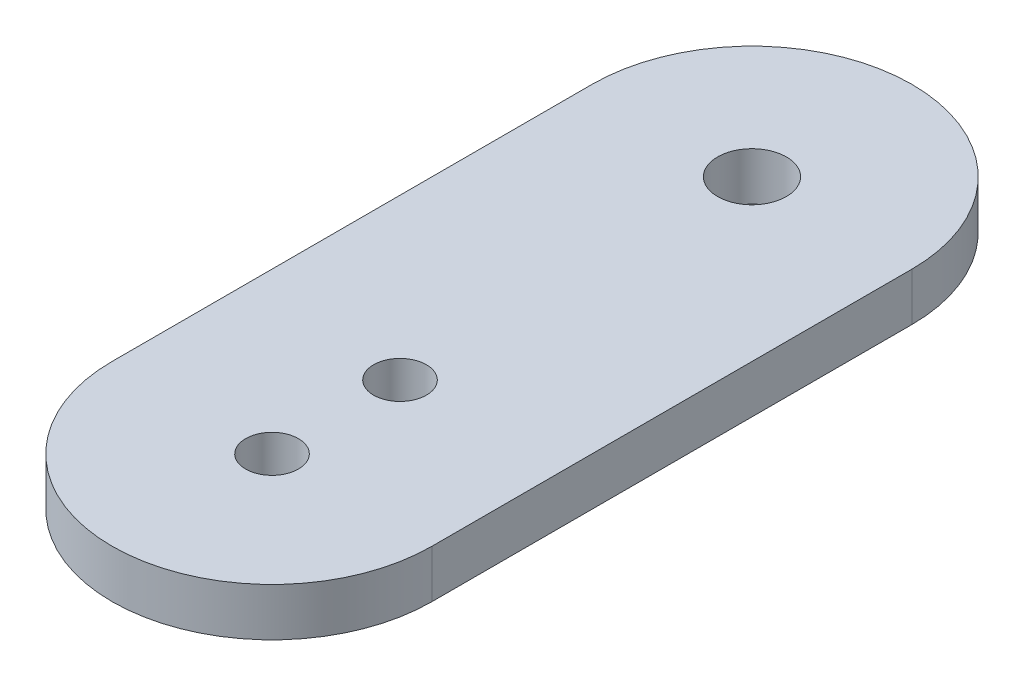
SolidWorks part; units mm, degrees
ref_plane "Front Plane" through (0, 0, 0) normal (0, 0, 1) x (1, 0, 0)
ref_plane "Top Plane" through (0, 0, 0) normal (0, 1, 0) x (1, 0, 0)
ref_plane "Right Plane" through (0, 0, 0) normal (1, 0, 0) x (0, 0, -1)
sketch "Sketch2" plane through (0, 0, 0) normal (0, 1, 0) x (1, 0, 0)
  line L0 (0, 0) -> (0, 30) construction
  line L1 (-10, 0) -> (-10, 30)
  line L2 (10, 0) -> (10, 30)
  arc A0 (-10, 0) -> (10, 0) centre (0, 0) ccw
  arc A1 (10, 30) -> (-10, 30) centre (0, 30) ccw
  point P3 (0, 15)
  dimension "D2" = 10
  dimension "D1" = 30
extrude "Boss-Extrude1" add sketch "Sketch2" along normal blind 3
sketch "Sketch3" plane through (0, 3, 0) normal (0, 1, 0) x (1, 0, 0)
  circle A0 centre (0, 0) radius 1.65
  circle A1 centre (0, 8) radius 1.65
  circle A2 centre (0, 30) radius 2.15
  dimension "D1" = 3.3
  dimension "D2" = 3.3
  dimension "D4" = 4.3
  dimension "D3" = 8
extrude "Cut-Extrude1" cut sketch "Sketch3" against normal blind 3
sketch "Sketch4" plane through (0, 0, 0) normal (0, -1, 0) x (1, 0, 0)
  line L0 (-10, -19.167) -> (10, -19.167) construction
  line L1 (-10, -30) -> (-10, 0) construction
  line L2 (10, 0) -> (10, -30) construction
  text T0 "Group 3" font "Century Gothic" height in points 9
extrude "Cut-Extrude2" cut sketch "Sketch4" against normal blind 0.1
